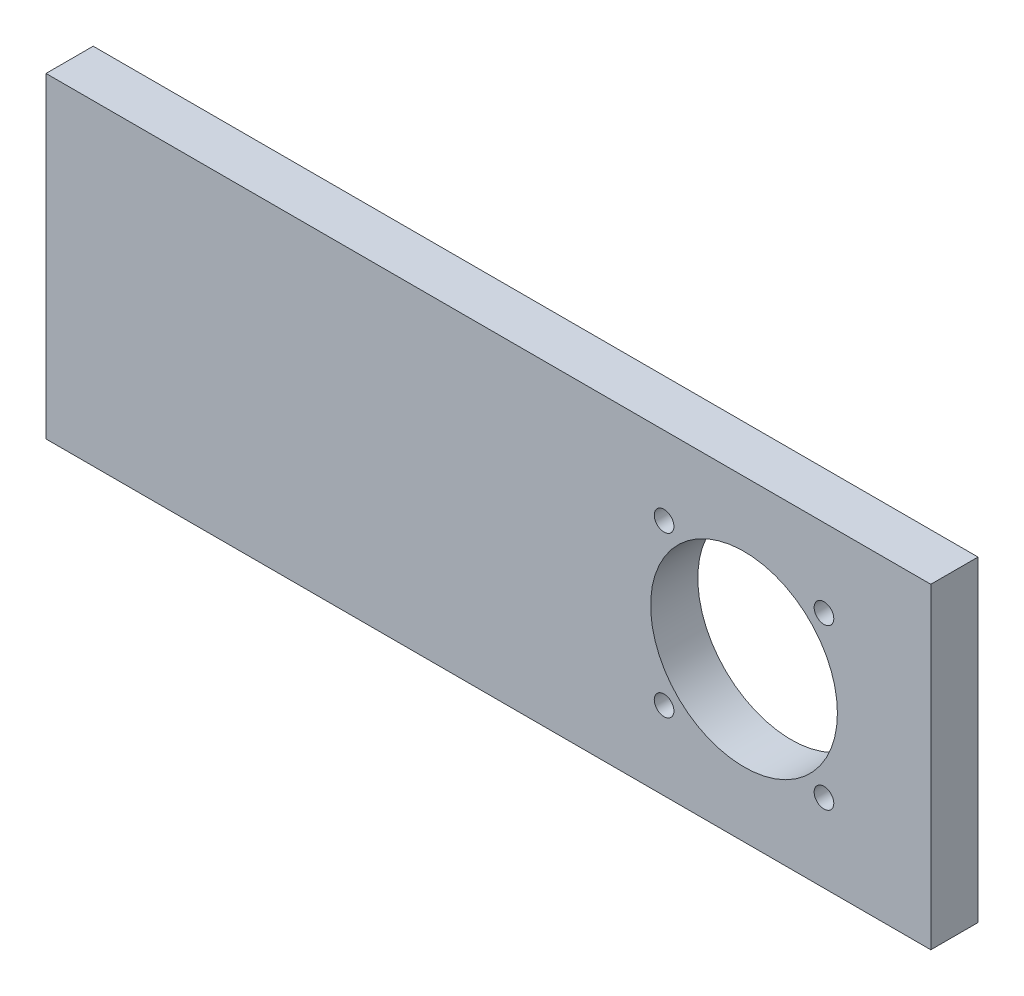
SolidWorks part; units mm, degrees
ref_plane "前视基准面" through (0, 0, 0) normal (0, 0, 1) x (1, 0, 0)
ref_plane "上视基准面" through (0, 0, 0) normal (0, 1, 0) x (1, 0, 0)
ref_plane "右视基准面" through (0, 0, 0) normal (1, 0, 0) x (0, 0, -1)
other "Configuration Table"
sketch "草图1" plane through (0, 0, 0) normal (0, 0, 1) x (1, 0, 0)
  line L0 (-225, 0) -> (225, 0) construction
  line L1 (-225, 80.5) -> (225, 80.5)
  line L2 (-225, 80.5) -> (-225, -80.5)
  line L3 (-225, -80.5) -> (225, -80.5)
  line L4 (225, 80.5) -> (225, -80.5)
  line L5 (-225, 80.5) -> (225, -80.5) construction
  line L6 (-225, -80.5) -> (225, 80.5) construction
  line L7 (0, 0) -> (0, 80.5) construction
  line L8 (130, 0) -> (130, 57.5) construction
  circle A0 centre (130, 0) radius 47.5
  circle A1 centre (130, 0) radius 57.5 construction
  circle A3 centre (170.6586, 40.6586) radius 5
  circle A4 centre (170.6586, -40.6586) radius 5
  circle A5 centre (89.3414, -40.6586) radius 5
  circle A6 centre (89.3414, 40.6586) radius 5
  point P0 (0, 0)
  point P16 (152.7417, -51.7291)
  point P17 (0, 0)
  point P25 (130, 0)
  dimension "D3" = 95
  dimension "D5" = 115
  dimension "D6" = 10
  dimension "D1" = 450
  dimension "D2" = 161
  dimension "D4" = 95
  dimension "D7" = 45
  dimension "D8" = 4
extrude "凸台-拉伸1" add sketch "草图1" along normal blind 24 contours L4 L3 L2 L1 | A0
extrude "切除-拉伸1" cut sketch "草图1<3>" against normal blind 18 from surface contours A6 | A3 | A4 | A5 region at (89.3414, 40.6586, 0) starting at face at (0, 0, 24)
sketch "草图1<3>" plane through (0, 0, 0) normal (0, 0, 1) x (1, 0, 0) same geometry as "草图1"
